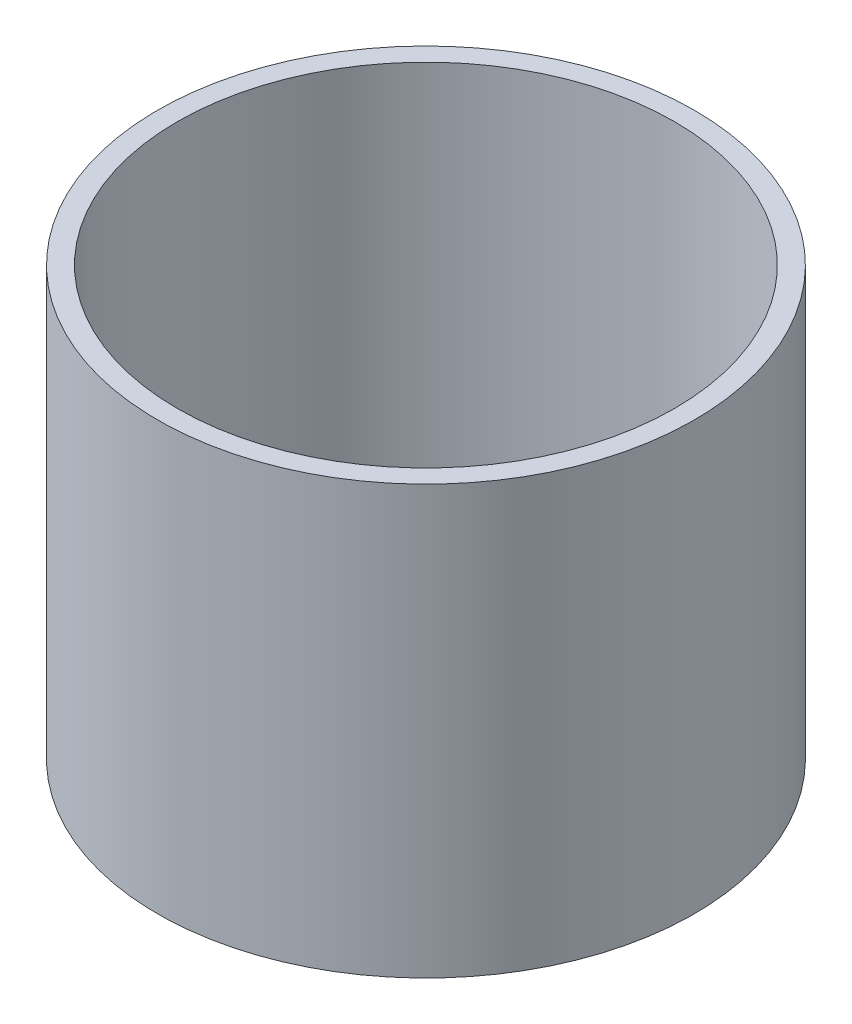
SolidWorks part; units mm, degrees
ref_plane "Front Plane" through (0, 0, 0) normal (0, 0, 1) x (1, 0, 0)
ref_plane "Top Plane" through (0, 0, 0) normal (0, 1, 0) x (1, 0, 0)
ref_plane "Right Plane" through (0, 0, 0) normal (1, 0, 0) x (0, 0, -1)
sketch "Sketch1" plane through (0, 0, 0) normal (0, 1, 0) x (1, 0, 0)
  circle A0 centre (0, 0) radius 13.55
  dimension "D1" = 27.1
extrude "Boss-Extrude1" add sketch "Sketch1" along normal blind 21.6
shell "Shell4" thickness 1 removed face at (0, 21.6, 13.55)
hole_wizard "M2x0.4 Tapped Hole1" positions "Sketch2" profile "Sketch3" tap size "M2x0.4" standard "ANSI Metric" end condition through all
sketch "Sketch2" plane through (0, 21.6, 0) normal (0, 1, 0) x (1, 0, 0)
  line L0 (13.55, 0) -> (-13.55, 0) construction
  line L2 (0, -13.55) -> (0, 13.55) construction
  circle A0 centre (0, 0) radius 13.55 construction
  point P0 (0, 8.7681)
  point P20 (8.7681, 0)
  point P21 (0, -8.7681)
  point P22 (-8.7681, 0)
  point P25 (-7.6301, 0)
  point P26 (0, -8.7502)
  dimension "D1" = 12.4
  dimension "D2" = 4
sketch "Sketch3" plane through (0, 21.6, -8.7681) normal (1, 0, 0) x (0, 0, 1)
  line L0 (0, 0) -> (0, 21.6)
  line L1 (0, 21.6) -> (0.8, 21.6)
  line L2 (0.8, 21.6) -> (0.8, 0)
  line L5 (0.8, 0) -> (0, 0)
  line L11 (0, -6.35) -> (0, 107.95) construction
  dimension "Thru Tap Drill Dia." = 1.6
  dimension "Thru Tap Drill Depth" = 21.6
cosmetic thread "Hole Thread6" parameters "D2"=2
cosmetic thread "Hole Thread7" parameters "D2"=2
cosmetic thread "Hole Thread8" parameters "D2"=2
cosmetic thread "Hole Thread9" parameters "D2"=2
sketch "Sketch4" plane through (0, 0, 0) normal (0, -1, 0) x (1, 0, 0)
  circle A0 centre (0, 0) radius 4.35
  dimension "D1" = 8.7
extrude "Boss-Extrude2" add sketch "Sketch4" along normal blind 1.5
